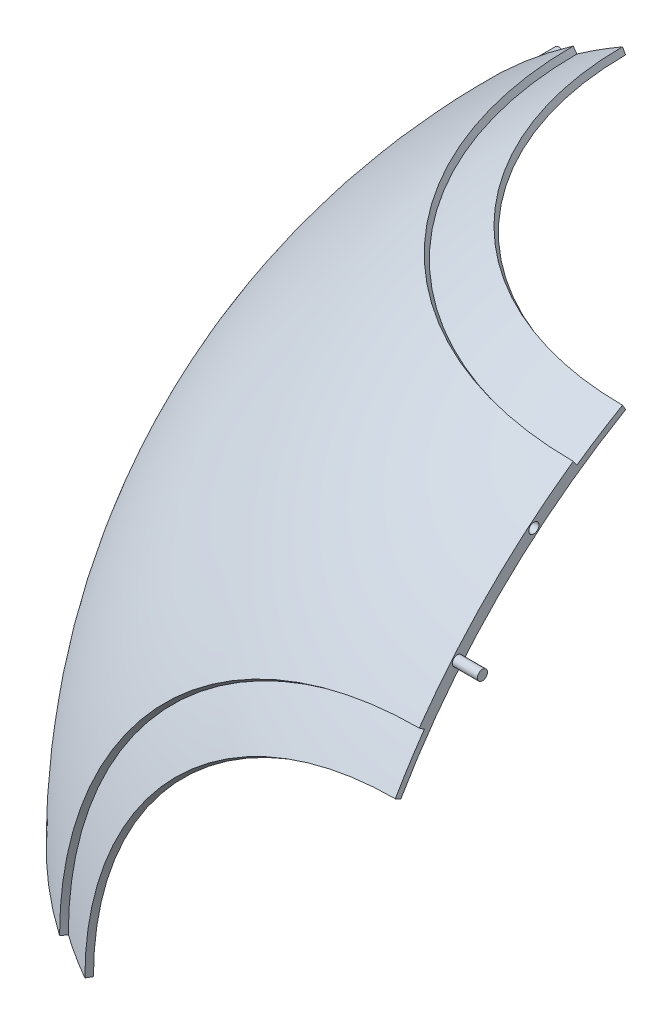
SolidWorks part; units mm, degrees
ref_plane "Front Plane" through (0, 0, 0) normal (0, 0, 1) x (1, 0, 0)
ref_plane "Top Plane" through (0, 0, 0) normal (0, 1, 0) x (1, 0, 0)
ref_plane "Right Plane" through (0, 0, 0) normal (1, 0, 0) x (0, 0, -1)
sketch "Sketch1" plane through (0, 0, 0) normal (0, 0, 1) x (1, 0, 0)
  line L0 (0, 0) -> (0, 282.4311)
  line L1 (-122.5, 212.1762) -> (-123.75, 214.3413)
  line L2 (-141.9602, 202.7401) -> (-143.3941, 204.788)
  line L3 (-245, 0) -> (-250, 0)
  arc A0 (-143.3941, 204.788) -> (-250, 0) centre (0, 0) ccw
  arc A1 (-123.75, 214.3413) -> (-141.9602, 202.7401) centre (0, 0) ccw
  arc A2 (-122.5, 212.1762) -> (-245, 0) centre (0, 0) ccw
  dimension "D1" = 500
  dimension "D2" = 495
  dimension "D3" = 490
  dimension "D4" = 5
  dimension "D5" = 30
revolve "Revolve1" add sketch "Sketch1" angle 90 about L0 region at (-214.3361, 123.747, 0)
sketch "Sketch2" plane through (0, 0, 0) normal (1, 0, 0) x (0, 0, -1)
  line L0 (0, 0) -> (-288.7114, 0)
  line L1 (-212.1762, 122.5) -> (-214.3413, 123.75)
  line L2 (-202.7401, 141.9602) -> (-204.788, 143.3941)
  arc A0 (-204.788, 143.3941) -> (-250, 0) centre (0, 0) ccw
  arc A1 (-212.1762, 122.5) -> (-245, 0) centre (0, 0) ccw
  arc A2 (-202.7401, 141.9602) -> (-214.3413, 123.75) centre (0, 0) ccw
  dimension "D1" = 495
  dimension "D2" = 490
  dimension "D3" = 5
  dimension "D4" = 30
revolve "Cut-Revolve2" cut sketch "Sketch2" angle 360 about L0 region at (0, 1.5098, 247.5)
sketch "Sketch3" plane through (0, 0, 0) normal (0, 0, -1) x (-1, 0, 0)
  line L0 (0, 0) -> (307.3195, 0)
  line L1 (202.7401, 141.9602) -> (204.788, 143.3941)
  line L2 (0, 0) -> (214.3413, 123.75)
  arc A0 (245, 0) -> (212.1762, 122.5) centre (0, 0) ccw
  arc A1 (250, 0) -> (204.788, 143.3941) centre (0, 0) ccw
  arc A2 (214.3413, 123.75) -> (202.7401, 141.9602) centre (0, 0) ccw
  dimension "D1" = 495
  dimension "D2" = 30
  dimension "D3" = 5
revolve "Cut-Revolve3" cut sketch "Sketch3" angle 360 about L0 region at (-238.1102, 63.8014, 0)
sketch "Sketch4" plane through (0, 0, 0) normal (0, 0, -1) x (-1, 0, 0)
  line L0 (0, 0) -> (143.3941, 204.788)
  circle A0 centre (0, 0) radius 247.5
  circle A1 centre (159.0899, 189.596) radius 2
  circle A2 centre (189.596, 159.0899) radius 2.025
  dimension "D1" = 495
  dimension "D2" = 4.05
  dimension "D5" = 4
  dimension "D3" = 10
  dimension "D4" = 5
extrude "Boss-Extrude1" add sketch "Sketch4" along normal blind 10 contours A0 A1 | A0 A1 region at (-159.6346, 190.2451, 0) region at (-158.5434, 188.9446, 0)
extrude "Cut-Extrude2" cut sketch "Sketch4<4>" against normal blind 10 contours A0 A2 | A0 A2 region at (-188.9365, 158.5365, 0) region at (-190.2532, 159.6414, 0)
sketch "Sketch4<4>" plane through (0, 0, 0) normal (0, 0, -1) x (-1, 0, 0) same geometry as "Sketch4"
sketch "Sketch5" plane through (0, 0, 0) normal (1, 0, 0) x (0, 0, -1)
  circle A0 centre (0, 0) radius 247.5
  circle A1 centre (-159.0899, 189.596) radius 2.025
  circle A2 centre (-189.596, 159.0899) radius 2
  dimension "D1" = 4
  dimension "D2" = 4.05
  dimension "D3" = 5
  dimension "D4" = 10
extrude "Boss-Extrude2" add sketch "Sketch5" along normal blind 10 contours A0 A2 | A0 A2 region at (0, 159.6346, 190.2451) region at (0, 158.5434, 188.9446)
extrude "Cut-Extrude3" cut sketch "Sketch5<3>" against normal blind 10 contours A0 A1 | A0 A1 region at (0, 188.9365, 158.5365) region at (0, 190.2532, 159.6414)
sketch "Sketch5<3>" plane through (0, 0, 0) normal (1, 0, 0) x (0, 0, -1) same geometry as "Sketch5"
sketch "Sketch6" plane through (0, 0, 0) normal (0, -1, 0) x (1, 0, 0)
  circle A0 centre (0, 0) radius 247.5
  circle A1 centre (-159.0899, 189.596) radius 2.025
  circle A2 centre (-189.596, 159.0899) radius 2
  dimension "D1" = 4.05
  dimension "D2" = 4
  dimension "D3" = 5
  dimension "D4" = 10
extrude "Boss-Extrude3" add sketch "Sketch6" along normal blind 10 contours A0 A2 | A2 region at (-190.2451, 0, 159.6346)
extrude "Cut-Extrude4" cut sketch "Sketch6<3>" against normal blind 10 contours A0 A1 | A0 A1 region at (-158.5365, 0, 188.9365) region at (-159.6414, 0, 190.2532)
sketch "Sketch6<3>" plane through (0, 0, 0) normal (0, -1, 0) x (1, 0, 0) same geometry as "Sketch6"
